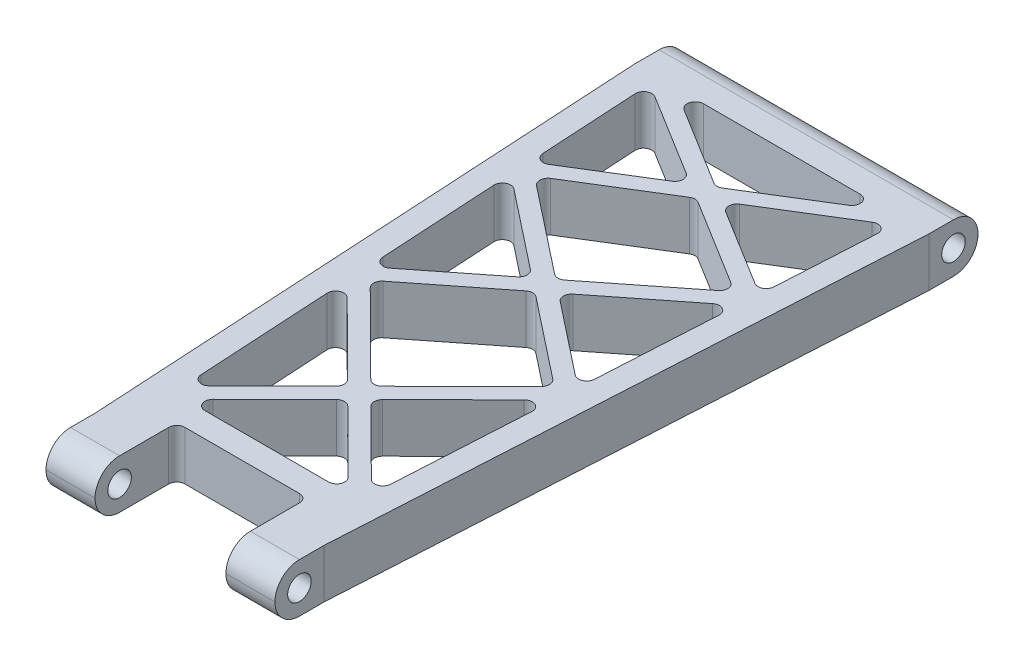
SolidWorks part; units mm, degrees
ref_plane "Front Plane" through (0, 0, 0) normal (0, 0, 1) x (1, 0, 0)
ref_plane "Top Plane" through (0, 0, 0) normal (0, 1, 0) x (1, 0, 0)
ref_plane "Right Plane" through (0, 0, 0) normal (1, 0, 0) x (0, 0, -1)
sketch "Sketch1" plane through (0, 0, 0) normal (0, 1, 0) x (1, 0, 0)
  line L0 (0, 0) -> (0, -120.65) construction
  line L1 (-28.575, 0) -> (28.575, 0) construction
  line L2 (-28.575, 4.7625) -> (-28.575, -4.7625)
  line L3 (28.575, 4.7625) -> (28.575, -4.7625)
  line L4 (-22.225, -120.65) -> (22.225, -120.65) construction
  line L5 (-22.225, -115.8875) -> (-22.225, -125.4125)
  line L6 (22.225, -115.8875) -> (22.225, -125.4125)
  line L7 (-28.575, -4.7625) -> (-22.225, -115.8875)
  line L8 (28.575, -4.7625) -> (22.225, -115.8875)
  line L9 (-22.225, -125.4125) -> (22.225, -125.4125)
  line L11 (-12.7, -125.4125) -> (-12.7, -109.5375)
  line L12 (-12.7, -109.5375) -> (12.7, -109.5375)
  line L13 (-28.575, 4.7625) -> (28.575, 4.7625)
  line L14 (-28.575, -4.7625) -> (28.575, -4.7625)
  line L15 (-22.225, -115.8875) -> (22.225, -115.8875)
  line L16 (-19.05, 4.7625) -> (-19.05, -4.7625)
  line L17 (-19.05, -4.7625) -> (19.05, -4.7625)
  line L18 (19.05, -4.7625) -> (19.05, 4.7625)
  line L19 (12.7, -109.5375) -> (12.7, -125.4125)
  point P6 (0, 0)
  point P9 (-28.575, 0)
  point P11 (28.575, 0)
  point P16 (0, -120.65)
  point P18 (-22.225, -120.65)
  point P21 (22.225, -120.65)
  point P29 (-13.7347, -112.4317)
  point P30 (0, 0)
  point P31 (0, 0)
  dimension "D1" = 9.525
  dimension "D2" = 57.15
  dimension "D3" = 9.525
  dimension "D4" = 44.45
  dimension "D5" = 120.65
  dimension "D6" = 9.525
  dimension "D7" = 9.525
  dimension "D8" = 9.525
  dimension "D9" = 9.525
  dimension "D10" = 15.875
extrude "Boss-Extrude1" add sketch "Sketch1" along normal blind 9.525 contours L16 L13 L2 L14 | L18 L14 L3 L13 | L7 L15 L8 L14 | L15 L5 L9 | L15 L19 L9 L6 | L14 L18 L13 L16 region at (-23.8125, 0, 0) region at (0, 0, 56.401) region at (0, 0, 0) region at (-17.4625, 0, 120.65) region at (23.8125, 0, 0) region at (17.4625, 0, 120.65)
sketch "Sketch6" plane through (-28.575, 0, 0) normal (-1, 0, 0) x (0, 0, 1)
  line L0 (-4.7625, 9.525) -> (-4.7625, 0) construction
  line L1 (115.8875, 9.525) -> (125.4125, 9.525) construction
  circle A0 centre (0, 4.7625) radius 2.286
  circle A1 centre (120.65, 4.7625) radius 2.286
  point P2 (-4.7625, 4.7625)
  point P3 (0, 0)
  point P9 (0, 0)
  point P10 (120.65, 9.525)
  dimension "D1" = 4.572
extrude "Cut-Extrude2" cut sketch "Sketch6" against normal through all both and the other way through all
fillet "Fillet5" radius 4.7625 6 edges at (0, 0, -4.7625) (0, 9.525, -4.7625) (17.4625, 0, 125.4125) (-17.4625, 0, 125.4125) (-17.4625, 9.525, 125.4125) (17.4625, 9.525, 125.4125)
sketch "Sketch7" plane through (0, 9.525, 0) normal (0, 1, 0) x (1, 0, 0)
  line L0 (-23.8047, -4.7625) -> (-18.0897, -104.775)
  line L1 (-17.4625, -115.7515) -> (-17.4625, -115.8875)
  line L2 (-17.4625, -115.8875) -> (-17.4625, -115.8875)
  line L6 (17.4625, -115.8875) -> (17.4625, -115.8875)
  line L7 (17.4625, -115.8875) -> (17.4625, -115.7515)
  line L8 (18.0897, -104.775) -> (23.8047, -4.7625)
  line L9 (23.8047, -4.7625) -> (23.8047, -4.7625)
  line L10 (23.8047, -4.7625) -> (-23.8047, -4.7625)
  line L11 (-23.8047, -4.7625) -> (-23.8047, -4.7625)
  line L12 (12.7, -109.5375) -> (12.7, -120.65)
  line L13 (12.7, -120.65) -> (22.225, -120.65)
  line L14 (22.225, -120.65) -> (22.225, -115.8875)
  line L15 (22.225, -115.8875) -> (28.575, -4.7625)
  line L16 (28.575, -4.7625) -> (28.575, 0)
  line L17 (28.575, 0) -> (-28.575, 0)
  line L18 (-28.575, 0) -> (-28.575, -4.7625)
  line L19 (-28.575, -4.7625) -> (-22.225, -115.8875)
  line L20 (-22.225, -115.8875) -> (-22.225, -120.65)
  line L21 (-22.225, -120.65) -> (-12.7, -120.65)
  line L22 (-12.7, -120.65) -> (-12.7, -109.5375)
  line L23 (-12.7, -109.5375) -> (12.7, -109.5375)
  line L24 (12.7, -109.5375) -> (12.7, -120.65)
  line L25 (12.7, -120.65) -> (22.225, -120.65)
  line L26 (22.225, -120.65) -> (22.225, -115.8875)
  line L27 (22.225, -115.8875) -> (28.575, -4.7625)
  line L28 (28.575, -4.7625) -> (28.575, 0)
  line L29 (28.575, 0) -> (-28.575, 0)
  line L30 (-28.575, 0) -> (-28.575, -4.7625)
  line L31 (-28.575, -4.7625) -> (-22.225, -115.8875)
  line L32 (-22.225, -115.8875) -> (-22.225, -120.65)
  line L33 (-22.225, -120.65) -> (-12.7, -120.65)
  line L34 (-12.7, -120.65) -> (-12.7, -109.5375)
  line L35 (-12.7, -109.5375) -> (12.7, -109.5375)
  line L36 (-17.4625, -104.775) -> (17.4625, -104.775) construction
  line L37 (-17.4625, -115.8875) -> (-17.4625, -104.775) construction
  line L38 (17.4625, -104.775) -> (17.4625, -115.8875) construction
  line L39 (-18.0897, -104.775) -> (18.0897, -104.775)
  line L40 (-23.8047, -4.7625) -> (-17.4625, -115.7515) construction
  line L41 (17.4625, -115.7515) -> (23.8047, -4.7625) construction
  line L42 (-23.8047, -4.7625) -> (22.1802, -33.192)
  line L43 (22.1802, -33.192) -> (-20.2669, -66.6748)
  line L44 (-20.2669, -66.6748) -> (18.0897, -104.775)
  line L45 (-24.6395, -6.1128) -> (19.4167, -33.35)
  line L46 (19.4167, -33.35) -> (-22.657, -66.5383)
  line L47 (-22.657, -66.5383) -> (16.971, -105.9013)
  line L48 (-22.9699, -3.4122) -> (24.9437, -33.0341)
  line L49 (24.9437, -33.0341) -> (-17.8768, -66.8114)
  line L50 (-17.8768, -66.8114) -> (19.2085, -103.6487)
  line L51 (23.8047, -4.7625) -> (-22.1802, -33.192) construction
  line L52 (-22.1802, -33.192) -> (20.2669, -66.6748) construction
  line L53 (20.2669, -66.6748) -> (-18.0897, -104.775) construction
  line L54 (22.9699, -3.4122) -> (-24.9437, -33.0341)
  line L55 (-24.9437, -33.0341) -> (17.8768, -66.8114)
  line L56 (17.8768, -66.8114) -> (-19.2085, -103.6487)
  line L57 (24.6395, -6.1128) -> (-19.4167, -33.35)
  line L58 (-19.4167, -33.35) -> (22.657, -66.5383)
  line L59 (22.657, -66.5383) -> (-16.971, -105.9013)
  dimension "D3" = 4.7625
  dimension "D1" = 0
  dimension "D2" = 4.7625
  dimension "D4" = 1.5875
  dimension "D5" = 1.5875
  dimension "D6" = 1.5875
  dimension "D7" = 1.5875
extrude "Cut-Extrude3" cut sketch "Sketch7" against normal through all both and the other way through all contours L54 L10 L48 | L54 L45 L0 | L8 L57 L48 | L57 L58 L46 L45 | L55 L0 L46 | L49 L58 L8 | L56 L55 L49 L50 | L56 L47 L0 | L8 L59 L50 | L47 L59 L39 region at (-16.3321, 9.525, 19.1887) region at (0, 9.525, 9.046) region at (-15, 9.525, 50.2459) region at (0, 9.525, 34.454) region at (16.3321, 9.525, 19.1887) region at (15, 9.525, 50.2459) region at (-13.5316, 9.525, 86.1703) region at (0, 9.525, 68.03) region at (13.5316, 9.525, 86.1703) region at (0, 9.525, 99.5313)
fillet "Fillet6" radius 1.5875 32 edges at (0, 4.7625, 84.5686) (-17.8768, 4.7625, 66.8114) (0, 4.7625, 52.71) (17.8768, 4.7625, 66.8114) (20.3774, 4.7625, 64.7401) (2.5633, 4.7625, 50.6881) (22.0592, 4.7625, 35.3094) (-22.2832, 4.7625, 31.3893) (-3.0189, 4.7625, 19.4794) (3.0189, 4.7625, 19.4794) (23.6942, 4.7625, 6.6972) (22.2832, 4.7625, 31.3893) (15.8371, 4.7625, 104.775) (-15.8371, 4.7625, 104.775) (0, 4.7625, 89.0438) (0, 4.7625, 17.6131) (-20.7858, 4.7625, 4.7625) (20.7858, 4.7625, 4.7625) (19.4167, 4.7625, 33.35) (0, 4.7625, 48.6661) (-19.4167, 4.7625, 33.35) (0, 4.7625, 21.3458) (-2.5633, 4.7625, 50.6881) (-20.3774, 4.7625, 64.7401) (-22.0592, 4.7625, 35.3094) (2.2526, 4.7625, 86.8062) (20.1313, 4.7625, 69.0471) (18.2107, 4.7625, 102.6576) (-18.2107, 4.7625, 102.6576) (-20.1313, 4.7625, 69.0471) (-2.2526, 4.7625, 86.8062) (-23.6942, 4.7625, 6.6972)
fillet "Fillet7" radius 1.5875 2 edges at (12.7, 4.7625, 109.5375) (-12.7, 4.7625, 109.5375)
